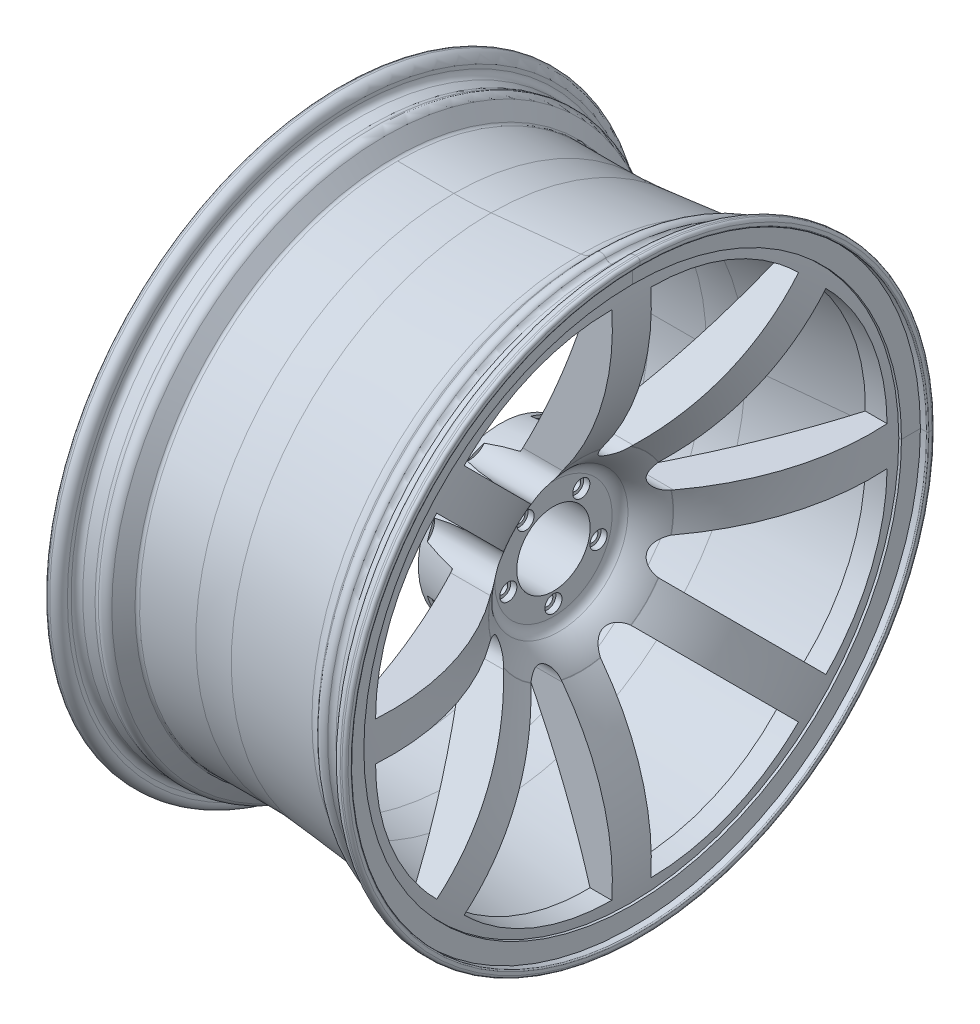
SolidWorks part; units mm, degrees
note: '?' marks a value the reader was unsure of.
ref_plane "Front Plane" through (0, 0, 0) normal (0, 0, 1) x (1, 0, 0)
ref_plane "Top Plane" through (0, 0, 0) normal (0, 1, 0) x (1, 0, 0)
ref_plane "Right Plane" through (0, 0, 0) normal (1, 0, 0) x (0, 0, -1)
sketch "Sketch1" plane through (0, 0, 0) normal (0, 0, 1) x (1, 0, 0)
  line L0 (0, 241.3) -> (0, 0) construction
  line L1 (0, 0) -> (-676.3289, 0) construction
  line L2 (0, 241.3) -> (-676.3289, 241.3) construction
  line L3 (-137.25, 238.8) -> (-137.25, 237.05)
  line L4 (-134.75, 241.3) -> (-133.25, 241.3)
  line L5 (-137.25, 237.05) -> (-132.25, 234.1632)
  line L6 (-132.25, 234.1632) -> (-137.25, 237.05)
  line L7 (-132.25, 234.1632) -> (-132.25, 226.05)
  line L8 (-126, 234.05) -> (-126, 231.024)
  line L9 (-121.4358, 226.043) -> (-112.2009, 225.235)
  line L10 (-100.2659, 223.4309) -> (-92.4575, 212.2793)
  line L11 (-90, 211) -> (-90, 206.5)
  line L12 (-90, 211) -> (-59.8531, 211) construction
  line L13 (-90, 206.5) -> (-68.8271, 206.5) construction
  line L14 (-97.7691, 210.2039) -> (-102.2375, 215.9232)
  line L15 (-106.4427, 218.2064) -> (-126.6855, 219.9774)
  arc A0 (-134.75, 241.3) -> (-137.25, 238.8) centre (-134.75, 238.8) ccw
  arc A1 (-133.25, 241.3) -> (-126, 234.05) centre (-133.25, 234.05) cw
  arc A2 (-126, 231.024) -> (-121.4358, 226.043) centre (-121, 231.024) ccw
  arc A3 (-112.2009, 225.235) -> (-108.8735, 225.7989) centre (-111.6182, 231.8957) ccw
  arc A4 (-108.8735, 225.7989) -> (-100.2659, 223.4309) centre (-106, 219.4159) cw
  arc A5 (-92.4575, 212.2793) -> (-90, 211) centre (-90, 214) ccw
  arc A6 (-90, 206.5) -> (-97.7691, 210.2039) centre (-90, 216.5) cw
  arc A7 (-102.2375, 215.9232) -> (-106.4427, 218.2064) centre (-106.9656, 212.2293) ccw
  arc A8 (-126.6855, 219.9774) -> (-132.25, 226.05) centre (-126.1543, 226.05) cw
  point P11 (-137.25, 241.3)
  dimension "D8" = 2.5
  dimension "D9" = 7.25
  dimension "D10" = 5
  dimension "D14" = 3
  dimension "D17" = 7
  dimension "D18" = 6.6861
  dimension "D21" = 10
  dimension "D23" = 6
  dimension "D1" = 241.3
  dimension "D2" = 4.25
  dimension "D3" = 137.25
  dimension "D4" = 4
  dimension "D5" = 120
  dimension "D6" = 5
  dimension "D7" = 15.25
  dimension "D11" = 5
  dimension "D12" = 4.5
  dimension "D13" = 125
  dimension "D15" = 90
  dimension "D16" = 206.5
  dimension "D19" = 16
  dimension "D20" = 0
  dimension "D22" = 38
  dimension "D24" = 6.5
revolve "Revolve3" add sketch "Sketch1" angle 360 about L1
fillet "Fillet1" radius 1 2 edges at (-132.25, 0, -234.1632) (-137.25, 0, -237.05)
ref_axis "Axis1" through (-121.4358, 0, 0) along (1, 0, 0)?
sketch3d "3DSketch1"
  line L0 (-90, 206.5, 0) -> (-44, 206.5, 0)
  line L1 (-13.4301, 208.0567, 0) -> (102.3064, 219.8748, 0)
  line L3 (0, 241.3, 0) -> (-676.3289, 241.3, 0) construction
  line L4 (-90, 211, 0) -> (-90, 206.5, 0)
  line L5 (-90, 211, 0) -> (-44, 211, 0)
  line L6 (-13.4301, 212.5567, 0) -> (65.3, 220.596, 0)
  line L7 (102.3064, 219.8748, 0) -> (102.3064, 235.3405, 0)
  line L8 (102.3064, 235.3405, 0) -> (108.3, 235.3405, 0)
  line L9 (108.3, 235.3405, 0) -> (108.3, 241.3, 0)
  line L10 (108.3, 241.3, 0) -> (96.8, 241.3, 0)
  line L11 (96.8, 241.3, 0) -> (96.8, 226.55, 0)
  line L12 (96.8, 226.55, 0) -> (81.2012, 224.9572, 0)
  line L14 (-90, 211, 0) -> (-59.8531, 211, 0) construction
  line L16 (65.3, 220.596, 0) -> (72.781, 228.077, 0)
  circle A0 centre (-90, 0, 0) radius 211 construction
  arc A2 (-44, 206.5, 0) -> (-13.4301, 208.0567, 0) centre (-44, 507.4323, 0) ccw
  arc A3 (72.781, 228.077, 0) -> (81.2012, 224.9572, 0) centre (76.2746, 224.5834, 0) ccw
  arc A4 (-44, 211, 0) -> (-13.4301, 212.5567, 0) centre (-44, 511.9323, 0) ccw
  point P4 (76.2746, 224.5834, -4.9407)
  point P8 (-44, 507.4323, 300.9323)
  point P14 (121, 0, 0)
  point P22 (-44, 511.9323, 300.9323)
  dimension "D2" = 300.9323
  dimension "D6" = 32.0254
  dimension "D7" = 11.5
  dimension "D14" = 4.5
  dimension "D15" = 676.3289
  dimension "D16" = 15.4657
  dimension "D9" = 4.9407
  dimension "D3" = 46
  dimension "D4" = 46
  dimension "D5" = 43
  dimension "D13" = 5.9936
  dimension "D8" = 108.3
  dimension "D10" = 14.75
  dimension "D11" = 5.9595
sweep "Sweep1" add profiles "3DSketch1" path edge at (-90, 0, -206.5)
fillet "Fillet2" radius 15 2 edges at (65.3, -155.9849, 155.9849) (65.3, 155.9849, -155.9849)
fillet "Fillet3" radius 5 4 edges at (81.2012, -159.0687, 159.0687) (81.2012, 159.0687, -159.0687) (96.8, 160.195, -160.195) (96.8, -160.195, 160.195)
fillet "Fillet4" radius 7.5 2 edges at (96.8, -170.6249, 170.6249) (96.8, 170.6249, -170.6249)
fillet "Fillet5" radius 2.5 2 edges at (108.3, -170.6249, 170.6249) (108.3, 170.6249, -170.6249)
fillet "Fillet6" radius 1 2 edges at (108.3, -166.4109, 166.4109) (108.3, 166.4109, -166.4109)
sketch "Sketch2" plane through (0, 0, 0) normal (0, 0, 1) x (1, 0, 0)
  line L0 (26.75, 73.5674) -> (-5.75, 67.25)
  line L1 (-5.75, 67.25) -> (-5.75, 30)
  line L2 (-5.75, 30) -> (37.5, 30)
  line L3 (37.5, 30) -> (37.5, 48)
  line L6 (59.9908, -220.0539) -> (59.9908, 220.0539) construction
  line L7 (87.1848, 223.2349) -> (92.3079, 223.2349)
  line L8 (92.3079, -226.0913) -> (92.3079, 226.0913) construction
  line L9 (99.125, 230.05) -> (100.3248, 219.6725)
  line L10 (102.3064, 219.8748) -> (-13.4301, 208.0567) construction
  arc A0 (26.75, 73.5674) -> (87.1848, 223.2349) centre (-587.7855, 408.7481) ccw
  arc A1 (37.5, 48) -> (42, 56.4853) centre (47.75, 48) cw
  arc A2 (42, 56.4853) -> (59.9908, 75.5) centre (7.974, 106.6974) ccw
  arc A4 (92.3079, 223.2349) -> (99.125, 230.05) centre (92.3079, 230.052) ccw
  arc A5 (100.3248, 219.6725) -> (59.9908, 75.5) centre (-96.2697, 196.9439) cw
  dimension "D8" = 700
  dimension "D13" = 10.25
  dimension "D1" = 5.75
  dimension "D2" = 43.25
  dimension "D3" = 67.25
  dimension "D4" = 30
  dimension "D5" = 18
  dimension "D6" = 11
  dimension "D7" = 32.5
  dimension "D14" = 4.5
  dimension "D15" = 75.5
  dimension "D16" = 22.4908
revolve "Revolve5" add sketch "Sketch2" angle 360 about L1
fillet "Fillet7" radius 1 1 edges at (26.75, 0, -73.5674)
sketch "Sketch3" plane through (0, 0, 0) normal (1, 0, 0) x (0, 0, -1)
  line L0 (-264.6142, 0) -> (288.5491, 0) construction
  line L1 (-230.4089, 230.4089) -> (0, 0) construction
  line L2 (0, 0) -> (241.0458, -241.0458) construction
  line L3 (0, 279.9593) -> (0, -345.2216) construction
  line L4 (0, 0) -> (257.0934, 257.0934) construction
  line L5 (0, 0) -> (-238.9612, -238.9612) construction
  line L6 (-15.926, 209.1849) -> (-15.926, 74.9353)
  line L7 (-41.7934, 64.2207) -> (-136.7222, 159.1495)
  line L8 (-102.9547, 125.382) -> (-115.2045, 115.2045) construction
  line L9 (-15.926, 195.01) -> (0, 195.01) construction
  line L10 (-209.1849, 15.926) -> (-74.9353, 15.926)
  line L11 (-64.2207, 41.7934) -> (-159.1495, 136.7222)
  line L12 (-41.7934, -64.2207) -> (-136.7222, -159.1495)
  line L13 (-15.926, -209.1849) -> (-15.926, -74.9353)
  line L14 (-64.2207, -41.7934) -> (-159.1495, -136.7222)
  line L15 (-209.1849, -15.926) -> (-74.9353, -15.926)
  line L16 (15.926, -209.1849) -> (15.926, -74.9353)
  line L17 (41.7934, -64.2207) -> (136.7222, -159.1495)
  line L18 (64.2207, -41.7934) -> (159.1495, -136.7222)
  line L19 (209.1849, -15.926) -> (74.9353, -15.926)
  line L20 (209.1849, 15.926) -> (74.9353, 15.926)
  line L21 (64.2207, 41.7934) -> (159.1495, 136.7222)
  line L22 (41.7934, 64.2207) -> (136.7222, 159.1495)
  line L23 (15.926, 209.1849) -> (15.926, 74.9353)
  arc A0 (-15.926, 74.9353) -> (-41.7934, 64.2207) centre (-31.0788, 74.9353) cw
  arc A1 (-136.7222, 159.1495) -> (-15.926, 209.1849) centre (-15.926, 38.3533) cw
  arc A2 (-74.9353, 15.926) -> (-64.2207, 41.7934) centre (-74.9353, 31.0788) ccw
  arc A3 (-159.1495, 136.7222) -> (-209.1849, 15.926) centre (-38.3533, 15.926) ccw
  arc A4 (-15.926, -74.9353) -> (-41.7934, -64.2207) centre (-31.0788, -74.9353) ccw
  arc A5 (-136.7222, -159.1495) -> (-15.926, -209.1849) centre (-15.926, -38.3533) ccw
  arc A6 (-74.9353, -15.926) -> (-64.2207, -41.7934) centre (-74.9353, -31.0788) cw
  arc A7 (-159.1495, -136.7222) -> (-209.1849, -15.926) centre (-38.3533, -15.926) cw
  arc A8 (15.926, -74.9353) -> (41.7934, -64.2207) centre (31.0788, -74.9353) cw
  arc A9 (136.7222, -159.1495) -> (15.926, -209.1849) centre (15.926, -38.3533) cw
  arc A10 (74.9353, -15.926) -> (64.2207, -41.7934) centre (74.9353, -31.0788) ccw
  arc A11 (159.1495, -136.7222) -> (209.1849, -15.926) centre (38.3533, -15.926) ccw
  arc A12 (74.9353, 15.926) -> (64.2207, 41.7934) centre (74.9353, 31.0788) cw
  arc A13 (159.1495, 136.7222) -> (209.1849, 15.926) centre (38.3533, 15.926) cw
  arc A14 (15.926, 74.9353) -> (41.7934, 64.2207) centre (31.0788, 74.9353) ccw
  arc A15 (136.7222, 159.1495) -> (15.926, 209.1849) centre (15.926, 38.3533) ccw
  dimension "D1" = 45
  dimension "D2" = 45
extrude "Cut-Extrude1" cut sketch "Sketch3" along normal blind 202.184 contours A1 L6 A0 L7 | A2 L11 A3 L10 | A6 L14 A7 L15 | A4 L12 A5 L13 | A8 L17 A9 L16 | A10 L18 A11 L19 | A12 L21 A13 L20 | A14 L22 A15 L23
sketch "Sketch4" plane through (0, 0, 0) normal (1, 0, 0) x (0, 0, -1)
  line L0 (0, 0) -> (0, 96.6538) construction
  line L1 (0, 241.3) -> (0, 0) construction
  line L2 (0, 0) -> (110.521, 35.9105) construction
  line L3 (0, 0) -> (80.4517, -110.7322) construction
  line L4 (0, 0) -> (-78.7123, -108.3382) construction
  line L5 (0, 0) -> (-126.6115, 41.1386) construction
  dimension "D1" = 72
  dimension "D2" = 72
  dimension "D3" = 72
  dimension "D4" = 72
hole_wizard "CBORE for M8 Cheese Slotted Head2" positions "Sketch10" profile "Sketch11" counterbore size "M8" standard "KS" end condition through all
sketch "Sketch10" plane through (37.5, 0, 0) normal (1, 0, 0) x (0, 0, -1)
  line L0 (-36.8964, -11.9884) -> (0, -38.7952) construction
  line L1 (0, -38.7952) -> (36.8964, -11.9884) construction
  line L2 (36.8964, -11.9884) -> (22.8032, 31.3859) construction
  line L3 (22.8032, 31.3859) -> (-22.8032, 31.3859) construction
  line L4 (-22.8032, 31.3859) -> (-36.8964, -11.9884) construction
  line L5 (0, -38.7952) -> (0, 0) construction
  line L6 (0, 0) -> (-36.8964, -11.9884) construction
  line L7 (36.8964, -11.9884) -> (0, 0) construction
  line L8 (0, 0) -> (22.8032, 31.3859) construction
  line L10 (-22.8032, 31.3859) -> (0, 0) construction
  point P0 (0, -38.7952)
  point P2 (-36.8964, -11.9884)
  point P4 (-22.8032, 31.3859)
  point P6 (22.8032, 31.3859)
  point P8 (36.8964, -11.9884)
  point P32 (0, -37.7083)
  point P33 (0, 0)
  point P34 (0, -39.6646)
  point P35 (0, -38.7952)
sketch "Sketch11" plane through (37.5, -38.7952, 0) normal (0, 1, 0) x (0, 0, -1)
  line L0 (0, 0) -> (0, 174.75)
  line L1 (0, 174.75) -> (4.5, 174.75)
  line L3 (4.5, 174.75) -> (4.5, 5)
  line L4 (4.5, 5) -> (7, 5)
  line L5 (7, 5) -> (7, 0)
  line L7 (7, 0) -> (0, 0)
  line L11 (0, -6.35) -> (0, 107.95) construction
  dimension "Thru Hole Dia." = 9
  dimension "Thru Hole Depth" = 174.75
  dimension "C'Bore Dia." = 14
  dimension "C'Bore Depth" = 5
fillet "Fillet8" radius 2.54 8 edges at (59.9908, 53.3866, -53.3866) (59.9908, 75.5, 0) (59.9908, 53.3866, 53.3866) (59.9908, 0, 75.5) (59.9908, -53.3866, 53.3866) (59.9908, -75.5, 0) (59.9908, -53.3866, -53.3866) (59.9908, 0, -75.5)
